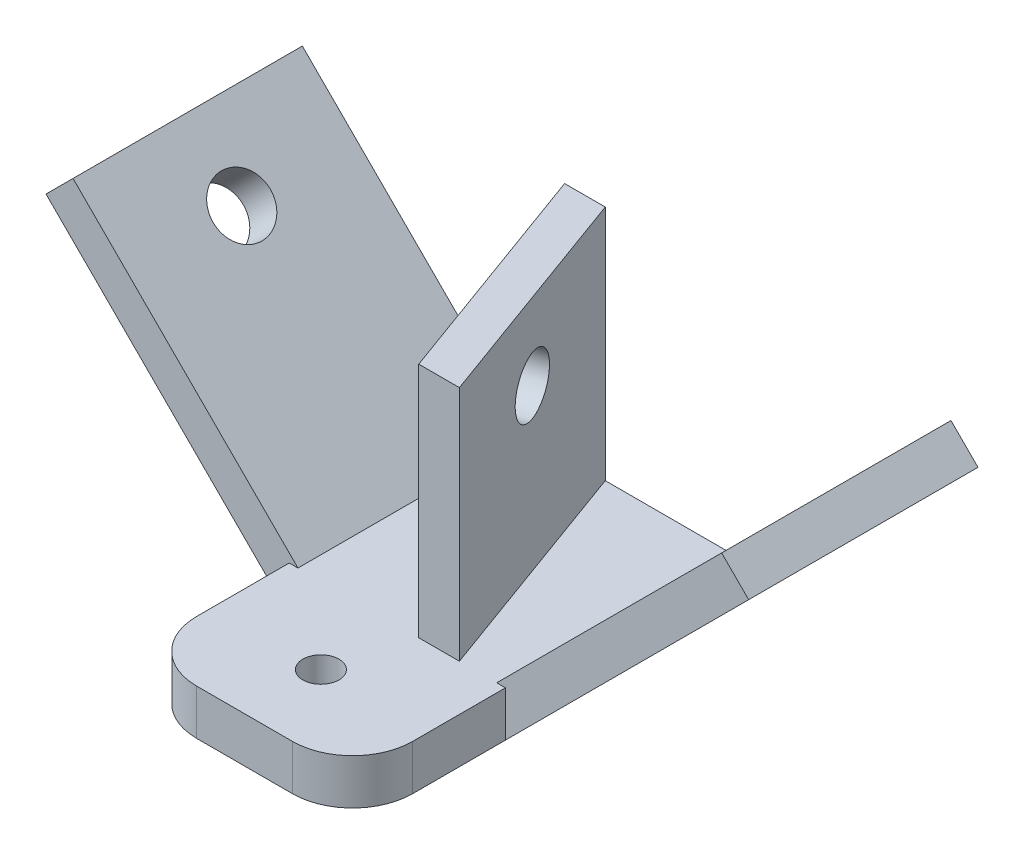
SolidWorks part; units mm, degrees
ref_plane "Front Plane" through (0, 0, 0) normal (0, 0, 1) x (1, 0, 0)
ref_plane "Top Plane" through (0, 0, 0) normal (0, 1, 0) x (1, 0, 0)
ref_plane "Right Plane" through (0, 0, 0) normal (1, 0, 0) x (0, 0, -1)
sketch "Sketch1" plane through (0, 0, 0) normal (0, 0, 1) x (1, 0, 0)
  line L0 (-53.8815, 53.8815) -> (0, 0)
  line L1 (0, 0) -> (53.8815, 53.8815)
  line L2 (53.8815, 53.8815) -> (58.3717, 49.3914)
  line L3 (58.3717, 49.3914) -> (0, -8.9803)
  line L4 (0, -8.9803) -> (-58.3717, 49.3914)
  line L5 (-58.3717, 49.3914) -> (-53.8815, 53.8815)
  line L6 (0, -8.9803) -> (0, 0) construction
  dimension "D1" = 6.35
  dimension "D2" = 76.2
extrude "Boss-Extrude1" add sketch "Sketch1" along normal mid plane 38.1
sketch "Sketch2" plane through (0, 0, 0) normal (0, 1, 0) x (1, 0, 0)
  line L0 (-10.3124, 19.05) -> (-3.5549, 19.05)
  line L1 (0, 19.05) -> (-53.8815, 19.05) construction
  line L2 (-3.5549, 19.05) -> (10.3124, -19.05)
  line L3 (53.8815, -19.05) -> (0, -19.05) construction
  line L4 (10.3124, -19.05) -> (3.5549, -19.05)
  line L5 (3.5549, -19.05) -> (-10.3124, 19.05)
  line L6 (-6.9336, 19.05) -> (6.9336, -19.05) construction
  line L7 (0, -19.05) -> (-53.8815, -19.05) construction
  point P10 (0, 0)
  dimension "D1" = 6.35
  dimension "D2" = 70
extrude "Boss-Extrude2" add sketch "Sketch2" against normal up to body and the other way blind 50.8 from offset 5.08 separate body
sketch "Sketch3" plane through (-4.4901, -4.4901, 0) normal (-0.7071, -0.7071, 0) x (0, 0, 1)
  line L0 (19.05, 76.2) -> (-19.05, 76.2) construction
  circle A0 centre (0, 63.5) radius 4.7625
  point P4 (0, 76.2)
  dimension "D1" = 9.525
  dimension "D2" = 12.7
extrude "Cut-Extrude1" cut sketch "Sketch3" against normal up to next
mirror "Mirror1" about plane through (0, 0, 0) normal (1, 0, 0) of "Cut-Extrude1"
sketch "Sketch4" plane through (2.9835, 0, -1.0859) normal (0.9397, 0, -0.342) x (-0.342, 0, -0.9397)
  line L0 (-21.4282, 55.88) -> (19.117, 55.88) construction
  circle A0 centre (-1.1556, 43.18) radius 4.7625
  point P4 (-1.1556, 55.88)
  dimension "D2" = 9.525
  dimension "D1" = 12.7
extrude "Cut-Extrude2" cut sketch "Sketch4" against normal up to next
sketch "Sketch5" plane through (0, 0, 19.05) normal (0, 0, 1) x (1, 0, 0)
  line L0 (-16.51, 16.51) -> (16.51, 16.51)
  line L1 (0, 0) -> (-53.8815, 53.8815) construction
  line L2 (53.8815, 53.8815) -> (10.3124, 10.3124) construction
  line L3 (16.51, 16.51) -> (0, 0)
  line L4 (0, 0) -> (-16.51, 16.51)
  dimension "D1" = 16.51
extrude "Boss-Extrude3" add sketch "Sketch5" against normal up to surface (38.1 mm away) up to face at (-2.7735, 32.3193, -19.05)
chamfer "Chamfer1" distance 25.4 angle 45 1 edges at (0, -8.9803, 0)
sketch "Sketch6" plane through (0, 8.9803, 0) normal (0, -1, 0) x (1, 0, 0)
  line L1 (-17.9605, 19.05) -> (17.9605, 19.05)
  line L2 (-17.9605, 19.05) -> (-17.9605, 44.45)
  line L3 (-17.9605, 44.45) -> (17.9605, 44.45)
  line L4 (17.9605, 19.05) -> (17.9605, 44.45)
  line L5 (-17.9605, 19.05) -> (17.9605, 44.45) construction
  line L6 (-17.9605, 44.45) -> (17.9605, 19.05) construction
  point P4 (0, 31.75)
  dimension "D1" = 25.4
extrude "Boss-Extrude4" add sketch "Sketch6" against normal up to surface (7.5297 mm away) up to face at (-9.9444, 16.51, 0)
sketch "Sketch7" plane through (0, 16.51, 0) normal (0, 1, 0) x (1, 0, 0)
  line L0 (-17.9605, -44.45) -> (-17.9605, -19.05) construction
  line L1 (17.9605, -44.45) -> (-17.9605, -44.45) construction
  circle A0 centre (0, -31.75) radius 3
  point P4 (-17.9605, -31.75)
  point P7 (0, -44.45)
  dimension "D1" = 6
extrude "Cut-Extrude3" cut sketch "Sketch7" against normal through all
fillet "Fillet1" radius 10 2 edges at (17.9605, 12.7451, 44.45) (-17.9605, 12.7451, 44.45)
